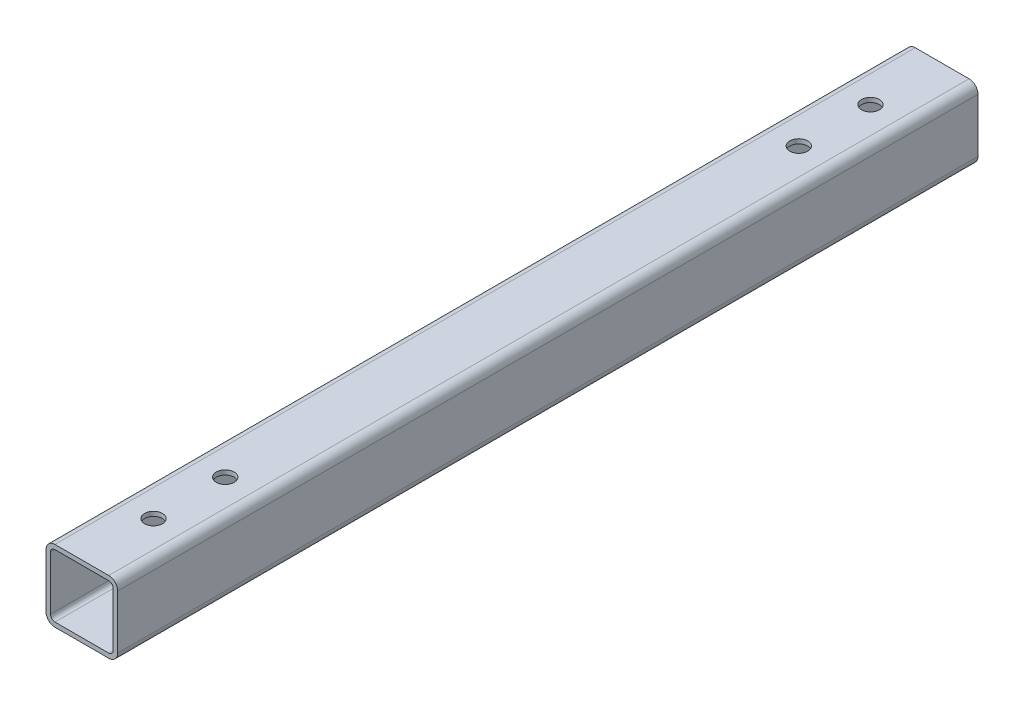
SolidWorks part; units mm, degrees
material "AISI Type 316L stainless steel"
ref_plane "Front" through (0, 0, 0) normal (0, 0, 1) x (1, 0, 0)
ref_plane "Top" through (0, 0, 0) normal (0, 1, 0) x (1, 0, 0)
ref_plane "Right" through (0, 0, 0) normal (1, 0, 0) x (0, 0, -1)
sketch "Sketch1" plane through (0, 0, 0) normal (0, 0, 1) x (1, 0, 0)
  line L0 (-12.7, 12.7) -> (12.7, 12.7)
  line L1 (-12.7, 12.7) -> (-12.7, -12.7)
  line L2 (12.7, -12.7) -> (-12.7, -12.7)
  line L3 (12.7, -12.7) -> (12.7, 12.7)
  line L4 (-12.7, -12.7) -> (12.7, 12.7) construction
  dimension "square" = 25.4
extrude "Base-Extrude" add sketch "Sketch1" along normal mid plane 304.8
fillet "Fillet1" radius 3.175 4 edges at (-12.7, 12.7, 0) (-12.7, -12.7, 0) (12.7, 12.7, 0) (12.7, -12.7, 0)
shell "Shell1" thickness 1.5875 removed face at (0, 0, -152.4) removed face at (0, 0, 152.4)
sketch "Sketch5" plane through (0, -12.7, 0) normal (0, -1, 0) x (1, 0, 0)
  line L0 (0, -152.4) -> (0, 152.4) construction
  line L1 (9.525, -152.4) -> (-9.525, -152.4) construction
  line L2 (9.525, 152.4) -> (-9.525, 152.4) construction
  circle A2 centre (0, 127) radius 3.175
  circle A3 centre (0, 101.6) radius 3.175
  circle A6 centre (0, -127) radius 3.175
  circle A7 centre (0, -101.6) radius 3.175
  dimension "D3" = 6.35
  dimension "D1" = 25.4
  dimension "D2" = 50.8
  dimension "D4" = 50.8
  dimension "D5" = 25.4
extrude "Cut-Extrude2" cut sketch "Sketch5" against normal through all
